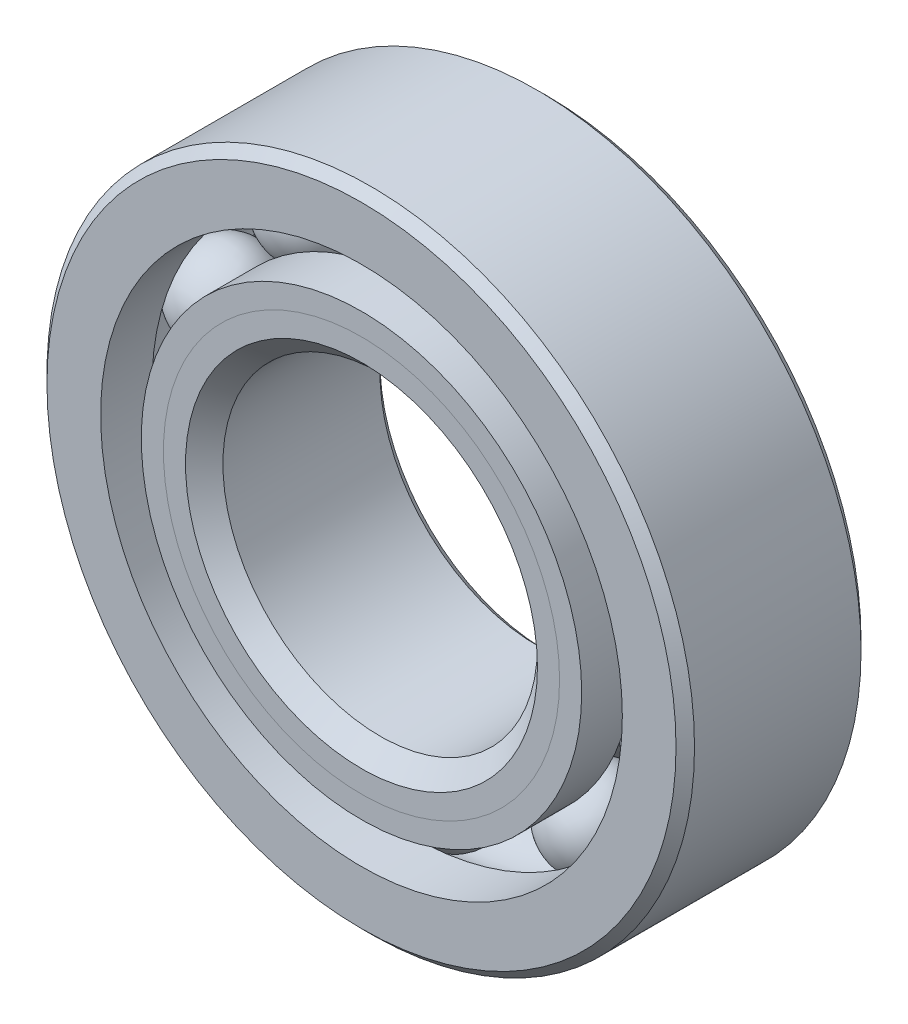
SolidWorks part; units mm, degrees
ref_plane "Front Plane" through (0, 0, 0) normal (0, 0, 1) x (1, 0, 0)
ref_plane "Top Plane" through (0, 0, 0) normal (0, 1, 0) x (1, 0, 0)
ref_plane "Right Plane" through (0, 0, 0) normal (1, 0, 0) x (0, 0, -1)
sketch "Sketch1" plane through (0, 0, 0) normal (1, 0, 0) x (0, 0, -1)
  line L0 (-5, 0) -> (5, 0) construction
  line L1 (0, 17.5) -> (0, -17.5) construction
  line L2 (4.5, 17.5) -> (-4.5, 17.5)
  line L3 (-4.5, 17.5) -> (-5, 17)
  line L4 (-5, 17) -> (-5, 14.0989)
  line L5 (-5, 14.0989) -> (-2.2222, 14.0989)
  line L6 (5, 14.0989) -> (2.2222, 14.0989)
  line L7 (5, 17) -> (5, 14.0989)
  line L8 (4.5, 17.5) -> (5, 17)
  line L9 (0, 17.5) -> (0, 13) construction
  line L10 (0, 13) -> (0, 8.5) construction
  arc A0 (-2.2222, 14.0989) -> (2.2222, 14.0989) centre (0, 13) cw
  point P14 (0, 8.5)
  dimension "Width" = 10
  dimension "OD" = 35
  dimension "D1" = 45
  dimension "D2" = 0.5
  dimension "D3" = 4.4444
  dimension "D4" = 1.0989
revolve "Revolve1" add sketch "Sketch1" angle 360 about L0
sketch "Sketch2" plane through (0, 0, 0) normal (1, 0, 0) x (0, 0, -1)
  line L0 (-5, 11.9011) -> (-2.2222, 11.9011)
  line L1 (-5, 17) -> (-5, -17) construction
  line L2 (-5, 11.9011) -> (-5, 10.7058)
  line L3 (-5, 10.7058) -> (-3.8047, 9.5105)
  line L4 (-3.8047, 9.5105) -> (0, 9.5105)
  line L5 (0, 17.5) -> (0, -17.5) construction
  line L6 (0, 9.5105) -> (0, 10.5209)
  line L7 (0, 10.5209) -> (0, 8.5) construction
  line L8 (-5, 11.9011) -> (-5, 9.5105) construction
  line L9 (-5, 9.5105) -> (-3.8047, 9.5105) construction
  arc A0 (-2.2222, 11.9011) -> (0, 10.5209) centre (0, 13) ccw
  arc A1 (2.2222, 14.0989) -> (-2.2222, 14.0989) centre (0, 13) ccw construction
  circle A2 centre (0, 13) radius 2.4791 construction
  dimension "D1" = 45
revolve "Revolve2" add sketch "Sketch2" angle 360 about L0
sketch "Sketch3" plane through (0, 0, 0) normal (1, 0, 0) x (0, 0, -1)
  line L0 (-5, 10.7058) -> (-3.8047, 9.5105)
  line L1 (-3.8047, 9.5105) -> (0, 9.5105)
  line L2 (0, 9.5105) -> (0, 10.5209)
  line L3 (-5, 10.7058) -> (-5, 9.5105)
  line L4 (-5, 11.9011) -> (-5, 9.5105) construction
  line L5 (-5, 9.5105) -> (-3.9895, 8.5)
  line L6 (-3.9895, 8.5) -> (4.5, 8.5)
  line L7 (4.5, 17.5) -> (4.5, -17.5) construction
  line L8 (4.5, 8.5) -> (5, 9)
  line L9 (5, -17) -> (5, 17) construction
  line L10 (5, 9) -> (5, 11.9011)
  line L11 (5, 11.9011) -> (2.2222, 11.9011)
  line L13 (4.5, 17.5) -> (5, 17) construction
  circle A0 centre (0, 13) radius 2.4791 construction
  arc A1 (2.2222, 11.9011) -> (0, 10.5209) centre (0, 13) cw
revolve "Revolve3" add sketch "Sketch3" angle 360 about L0
sketch "Sketch4" plane through (0, 0, 0) normal (1, 0, 0) x (0, 0, -1)
  line L0 (-2.4791, 13) -> (2.4791, 13)
  circle A1 centre (0, 13) radius 2.4791 construction
  arc A2 (-2.4791, 13) -> (2.4791, 13) centre (0, 13) cw
  arc A3 (2.2222, 14.0989) -> (-2.2222, 14.0989) centre (0, 13) ccw construction
revolve "Revolve4" add sketch "Sketch4" angle 360 about L0
ref_axis "Axis1" through (0, 0, -5) along (0, 0, 1)
pattern_circular "CirPattern1" count 10 every 36 about axis through (0, 0, -5) along (0, 0, 1) of bodies 104
equation "\"D2@Sketch1\" = \"Width@Sketch1\"*.05"
equation "\"D3@Sketch1\" = \"Width@Sketch1\"/2.25"
equation "\"D4@Sketch1\" = (((\"OD@Sketch1\"-\"Width@Sketch1\")/2)/3.25)/3.5"
equation "\"D2@CirPattern1\" = 360/\"Balls@CirPattern1\""
